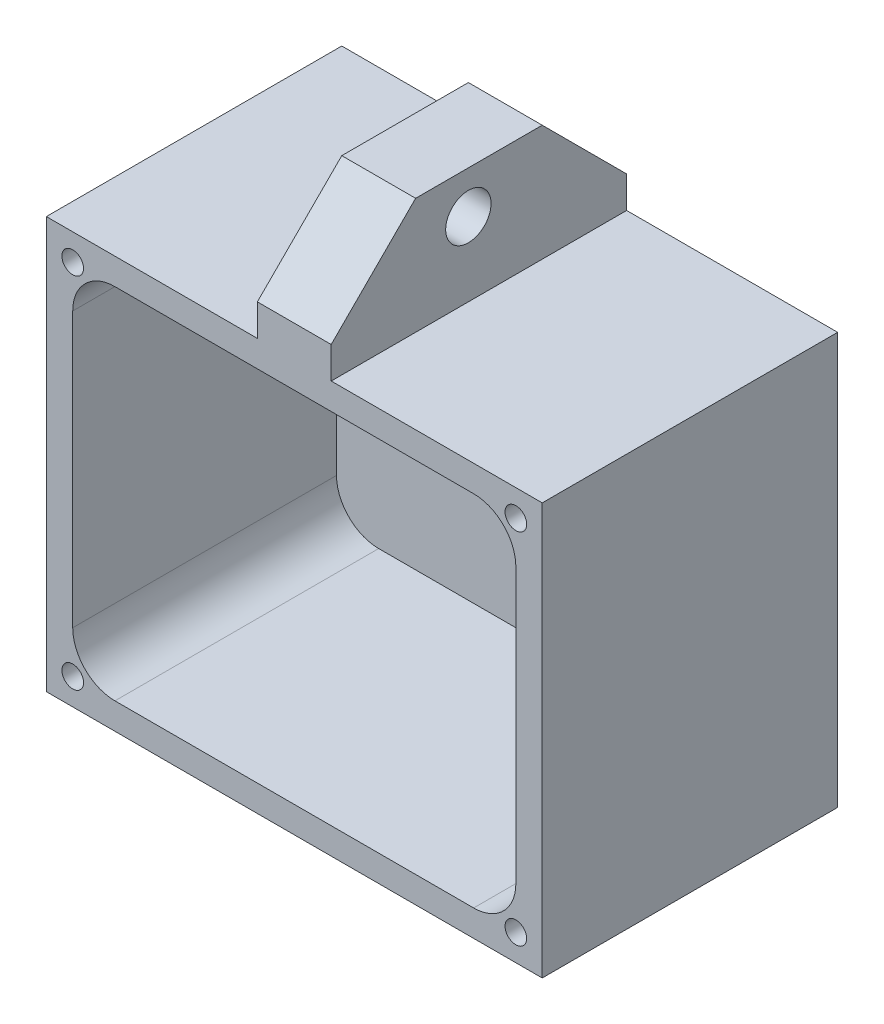
SolidWorks part; units mm, degrees
ref_plane "前视基准面" through (0, 0, 0) normal (0, 0, 1) x (1, 0, 0)
ref_plane "上视基准面" through (0, 0, 0) normal (0, 1, 0) x (1, 0, 0)
ref_plane "右视基准面" through (0, 0, 0) normal (1, 0, 0) x (0, 0, -1)
sketch "草图1" plane through (0, 0, 0) normal (0, 0, 1) x (1, 0, 0)
  line L1 (-23.5, -19.5) -> (23.5, -19.5)
  line L2 (-23.5, -19.5) -> (-23.5, 19.5)
  line L3 (-23.5, 19.5) -> (23.5, 19.5)
  line L4 (23.5, -19.5) -> (23.5, 19.5)
  line L5 (-23.5, -19.5) -> (23.5, 19.5) construction
  line L6 (-23.5, 19.5) -> (23.5, -19.5) construction
  point P0 (0, 0)
  dimension "D1" = 47
  dimension "D2" = 39
extrude "凸台-拉伸1" add sketch "草图1" along normal blind 28
sketch "草图4" plane through (0, 0, 28) normal (0, 0, 1) x (1, 0, 0)
  line L1 (-21, 17) -> (21, 17)
  line L2 (-21, 17) -> (-21, -17)
  line L3 (-21, -17) -> (21, -17)
  line L4 (21, 17) -> (21, -17)
  line L5 (-21, 17) -> (21, -17) construction
  line L6 (-21, -17) -> (21, 17) construction
  point P0 (0, 0)
  dimension "D1" = 42
  dimension "D2" = 34
extrude "切除-拉伸1" cut sketch "草图4" against normal offset from surface (25 mm away) 3 up to face at (0, 0, 0)
fillet "圆角1" radius 4 4 edges at (21, -17, 15.5) (-21, -17, 15.5) (-21, 17, 15.5) (21, 17, 15.5)
hole_wizard "M2.5 螺纹孔1" positions "草图6" profile "草图5" tap size "M2.5" standard "GB"
sketch "草图6" plane through (0, 0, 28) normal (0, 0, 1) x (1, 0, 0)
  line L1 (-21, -17) -> (21, -17)
  line L2 (-21, -17) -> (-21, 17)
  line L3 (-21, 17) -> (21, 17)
  line L4 (21, -17) -> (21, 17)
  line L5 (-21, -17) -> (21, 17) construction
  line L6 (-21, 17) -> (21, -17) construction
  line L7 (0, 0) -> (21, 0) construction
  line L9 (0, 0) -> (0, 17) construction
  point P2 (21, 17)
  point P5 (-21, -17)
  point P6 (-21, 17)
  point P7 (21, -17)
  dimension "D1" = 42
  dimension "D2" = 34
sketch "草图5" plane through (21, 17, 28) normal (1, 0, 0) x (0, -1, 0)
  line L0 (0, 0) -> (0, 6.9659)
  line L1 (0, 6.9659) -> (1.025, 6.35)
  line L2 (1.025, 6.35) -> (1.025, 0)
  line L5 (1.025, 0) -> (0, 0)
  line L10 (0, 6.9659) -> (-1.025, 6.35) construction
  line L11 (0, -6.35) -> (0, 107.95) construction
  dimension "螺纹孔钻头直径" = 2.05
  dimension "螺纹孔钻头深度" = 6.35
  dimension "导头角度" = 118
cosmetic thread "孔螺蚊线1" parameters "D1"=5, "D2"=2.5
cosmetic thread "孔螺蚊线2" parameters "D1"=5, "D2"=2.5
cosmetic thread "孔螺蚊线3" parameters "D1"=5, "D2"=2.5
cosmetic thread "孔螺蚊线4" parameters "D1"=5, "D2"=2.5
hole_wizard "M3 螺纹孔1" positions "草图8" profile "草图9" tap size "M3" standard "GB" end condition up to next
sketch "草图8" plane through (0, 0, 0) normal (0, 0, -1) x (-1, 0, 0)
  line L0 (0, 0) -> (0, 13.3443) construction
  line L1 (23.5, -19.5) -> (-23.5, -19.5) construction
  point P0 (-12, -6.5)
  point P2 (12, -6.5)
  point P10 (0, 10.5)
  dimension "D1" = 24
  dimension "D2" = 17
  dimension "D3" = 13
sketch "草图9" plane through (12, -6.5, 0) normal (1, 0, 0) x (0, 1, 0)
  line L0 (0, 0) -> (0, 3)
  line L1 (0, 3) -> (1.25, 3)
  line L2 (1.25, 3) -> (1.25, 0)
  line L5 (1.25, 0) -> (0, 0)
  line L11 (0, -6.35) -> (0, 107.95) construction
  dimension "通孔螺纹孔钻头直径" = 2.5
  dimension "通孔螺纹孔钻头深度" = 3
cosmetic thread "孔螺蚊线5" parameters "D2"=3
cosmetic thread "孔螺蚊线6" parameters "D2"=3
cosmetic thread "孔螺蚊线7" parameters "D2"=3
sketch "草图10" plane through (0, 0, 3) normal (0, 0, 1) x (1, 0, 0)
  circle A0 centre (0, 0) radius 6
  dimension "D2" = 12
extrude "切除-拉伸2" cut sketch "草图10" against normal up to next
sketch "草图11" plane through (0, 0, 0) normal (0, 0, -1) x (-1, 0, 0)
  line L0 (-23.5, 19.5) -> (23.5, 19.5) construction
  line L1 (-3.5, 30.5) -> (3.5, 30.5)
  line L2 (-3.5, 30.5) -> (-3.5, 19.5)
  line L3 (-3.5, 19.5) -> (3.5, 19.5)
  line L4 (3.5, 30.5) -> (3.5, 19.5)
  line L5 (-3.5, 30.5) -> (3.5, 19.5) construction
  line L6 (-3.5, 19.5) -> (3.5, 30.5) construction
  point P0 (0, 25)
  dimension "D1" = 7
  dimension "D2" = 11
extrude "凸台-拉伸2" add sketch "草图11" against normal up to surface (28 mm away) up to face at (22.025, 17, 28)
hole_wizard "M4 间隙孔1" positions "草图13" profile "草图12" hole size "M4" standard "GB" end condition up to next
sketch "草图13" plane through (3.5, 0, 0) normal (1, 0, 0) x (0, 0, -1)
  line L0 (-28, 19.5) -> (0, 19.5) construction
  line L1 (-28, 19.5) -> (-28, 30.5) construction
  point P0 (-15, 26.5)
  dimension "D1" = 7
  dimension "D2" = 13
sketch "草图12" plane through (3.5, 26.5, 15) normal (0, 1, 0) x (0, 0, -1)
  line L0 (0, 0) -> (0, 7)
  line L1 (0, 7) -> (2.15, 7)
  line L2 (2.15, 7) -> (2.15, 0)
  line L5 (2.15, 0) -> (0, 0)
  line L11 (0, -6.35) -> (0, 107.95) construction
  dimension "通孔孔直径" = 4.3
  dimension "通孔孔深度" = 7
chamfer "倒角1" distance 8 angle 45 2 edges at (0, 30.5, 0) (0, 30.5, 28)
